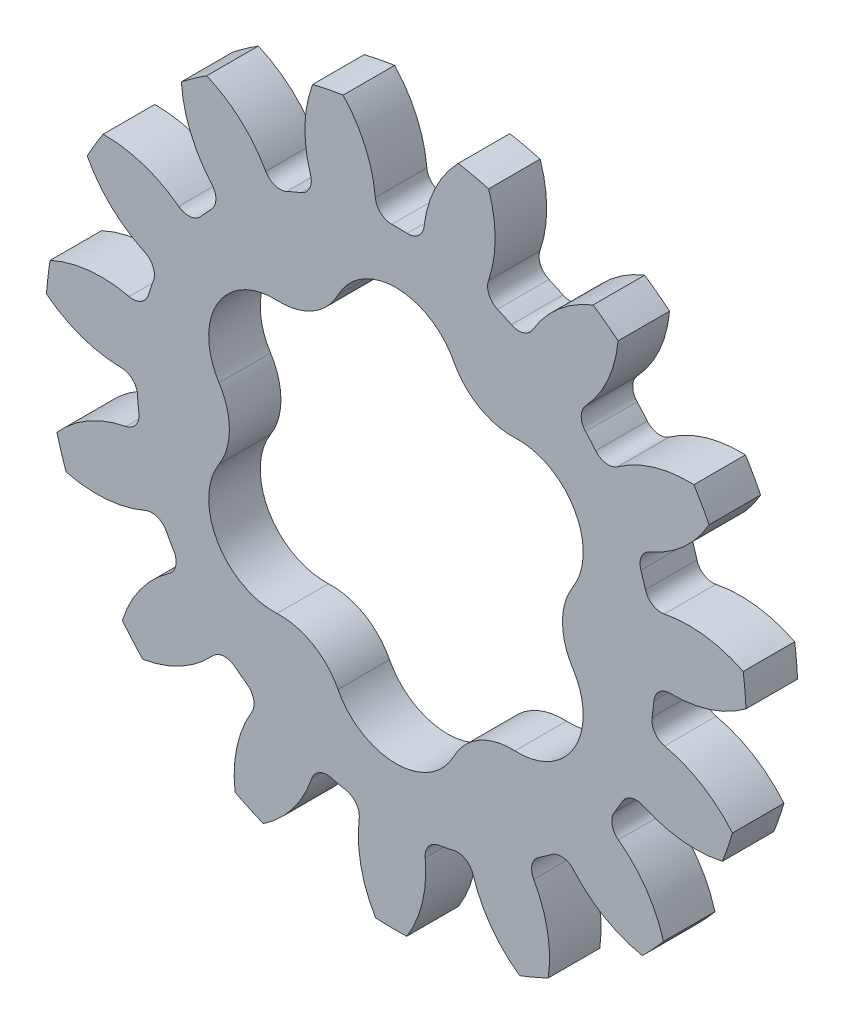
SolidWorks part; units mm, degrees
material "6061-T6 (SS)"
ref_plane "Front" through (0, 0, 0) normal (0, 0, 1) x (1, 0, 0)
ref_plane "Top" through (0, 0, 0) normal (0, 1, 0) x (1, 0, 0)
ref_plane "Right" through (0, 0, 0) normal (1, 0, 0) x (0, 0, -1)
sketch "Sketch3" plane through (0, 0, 0) normal (0, 0, 1) x (1, 0, 0)
  circle A0 centre (0, 0) radius 21.59
  dimension "od" = 43.18
extrude "gearBody" add sketch "Sketch3" along normal blind 3.175
sketch "Sketch2" plane through (0, 0, 0) normal (0, 0, 1) x (1, 0, 0)
  line L0 (0, 0) -> (17.0393, 7.0579) construction
  line L1 (21.9771, -8.1843) -> (0, 0) construction
  line L2 (0, 0) -> (36.3143, 0) construction
  line L3 (19.0486, -0.229) -> (18.5705, -4.2473) construction
  line L5 (18.8096, -2.2381) -> (0, 0) construction
  line L7 (0, 0) -> (18.4432, 0) construction
  arc A0 (18.4395, -0.3701) -> (18.0115, -3.9672) centre (0, 0) ccw construction
  arc A1 (21.5666, 1.0048) -> (20.7286, -6.0375) centre (0, 0) ccw construction
  arc A2 (19.0486, -0.229) -> (18.5705, -4.2473) centre (0, 0) ccw construction
  arc A3 (15.7767, -2.3527) -> (15.8883, -1.4151) centre (0, 0) ccw
  arc A4 (21.9771, -8.1843) -> (16.5518, -3.4814) centre (14.9073, -10.8592) ccw
  arc A5 (21.9771, -8.1843) -> (23.2839, 2.7987) centre (0, 0) ccw
  arc A6 (23.2839, 2.7987) -> (16.9066, -0.4998) centre (17.0393, 7.0579) cw
  arc A7 (15.8883, -1.4151) -> (16.9066, -0.4998) centre (16.8889, -1.5042) cw
  arc A8 (16.5518, -3.4814) -> (15.7767, -2.3527) centre (16.7703, -2.5009) cw
  point P6 (23.2839, 2.7987)
  point P22 (21.9771, -8.1843)
  dimension "baseDia" = 36.8864
  dimension "od" = 43.18
  dimension "pd" = 38.1
  dimension "rd" = 31.9024
  dimension "rFillet" = 1.0046
  dimension "pointX" = 23.2839
  dimension "pointY" = 2.7987
  dimension "CTT" = 4.0183
  dimension "flankCenterAngle" = 22.5
extrude "toothCut" cut sketch "Sketch2" along normal through all
pattern_circular "CirPattern1" count 15 over 360 about axis through (0, 0, 3.175) along (0, 0, -1) of "toothCut"
ref_axis "toothSpace" through (0, 0, 0) along (0.993, -0.1182, 0)
ref_axis "Axis2" through (20.4399, -6.9526, 0) along (-0.9467, 0.322, 0)
sketch "hub1Dia" plane through (0, 0, 0) normal (0, 0, -1) x (-1, 0, 0)
  circle A0 centre (0, 0) radius 12.7
  dimension "hub1Dia" = 25.4
sketch "hub2Dia" plane through (0, 0, 3.175) normal (0, 0, 1) x (1, 0, 0)
  circle A0 centre (0, 0) radius 12.7
  dimension "hub2dia" = 25.4
sketch "boreDia" plane through (0, 0, 0) normal (0, 0, 1) x (1, 0, 0)
  circle A0 centre (0, 0) radius 1.5
  dimension "boreDia" = 3
extrude "bore" cut sketch "boreDia" against normal mid plane 25400
sketch "kwy1sketch" plane through (0, 0, 0) normal (0, 0, 1) x (1, 0, 0)
  line L0 (-5.199, 1.3723) -> (0, 0) construction
  line L1 (29.2504, 5.4145) -> (22.7682, -19.1445)
  line L2 (22.7682, -19.1445) -> (-7.9305, -11.0417)
  line L3 (29.2504, 5.4145) -> (-1.4483, 13.5172)
  line L4 (-7.9305, -11.0417) -> (0, 0)
  line L5 (0, 0) -> (-1.4483, 13.5172)
  line L6 (0, 0) -> (15.8395, -1.8847) construction
  line L7 (26.0093, -6.865) -> (0, 0) construction
  arc A7 (15.7767, -2.3527) -> (15.8883, -1.4151) centre (0, 0) ccw construction
  point P9 (26.0093, -6.865)
  point P13 (-0.8672, 0.2289)
  dimension "kwy1width" = 25.4
  dimension "kwy1depth" = 26.9
  dimension "kwy1angle" = 8
  dimension "kwy1Depth2" = 31.75
sketch "kwy2sketch" plane through (0, 0, 0) normal (0, 0, 1) x (1, 0, 0)
  line L0 (15.8395, -1.8847) -> (0, 0) construction
  line L1 (0, 0) -> (-3.211, -1.8699) construction
  line L2 (16.8545, 24.5117) -> (29.6367, 2.5623)
  line L3 (29.6367, 2.5623) -> (2.2, -13.4154)
  line L4 (16.8545, 24.5117) -> (-10.5822, 8.534)
  line L5 (2.2, -13.4154) -> (0, 0)
  line L6 (0, 0) -> (-10.5822, 8.534)
  arc A2 (15.7767, -2.3527) -> (15.8883, -1.4151) centre (0, 0) ccw construction
  point P10 (23.2456, 13.537)
  dimension "kwy2angle" = 37
  dimension "kwy2Width" = 25.4
  dimension "kwy2depth" = 26.9
  dimension "kwy2Depth2" = 31.75
sketch "kwy3sketch" plane through (0, 0, 0) normal (0, 0, 1) x (1, 0, 0)
  line L0 (15.8395, -1.8847) -> (0, 0) construction
  line L1 (0, 0) -> (-0.686, -2.5992) construction
  line L2 (-5.4145, 29.2504) -> (19.1445, 22.7682)
  line L3 (19.1445, 22.7682) -> (11.0417, -7.9305)
  line L4 (-5.4145, 29.2504) -> (-13.5172, -1.4483)
  line L5 (11.0417, -7.9305) -> (0, 0)
  line L6 (-13.5172, -1.4483) -> (0, 0)
  point P10 (6.865, 26.0093)
  dimension "kwy3angle" = 82
  dimension "kwy3depth" = 26.9
  dimension "kwy3width" = 25.4
  dimension "kwy3Depth2" = 31.75
sketch "kwy4sketch" plane through (0, 0, 0) normal (0, 0, 1) x (1, 0, 0)
  line L0 (15.8395, -1.8847) -> (0, 0) construction
  line L1 (0, 0) -> (1.0577, -1.8163) construction
  line L2 (-2.5623, 29.6367) -> (-24.5117, 16.8545)
  line L3 (-24.5117, 16.8545) -> (-8.534, -10.5822)
  line L4 (-8.534, -10.5822) -> (0, 0)
  line L5 (13.4154, 2.2) -> (0, 0)
  line L6 (-2.5623, 29.6367) -> (13.4154, 2.2)
  point P15 (-13.537, 23.2456)
  dimension "kwy4angle" = 127
  dimension "kwy4depth" = 26.9
  dimension "kwy4width" = 25.4
  dimension "kwy4Depth2" = 31.75
sketch "kwy5sketch" plane through (0, 0, 0) normal (0, 0, 1) x (1, 0, 0)
  line L0 (15.8395, -1.8847) -> (0, 0) construction
  line L1 (0, 0) -> (1.7454, -0.4607) construction
  line L2 (-22.7682, 19.1445) -> (-29.2504, -5.4145)
  line L3 (-29.2504, -5.4145) -> (1.4483, -13.5172)
  line L4 (-22.7682, 19.1445) -> (7.9305, 11.0417)
  line L5 (1.4483, -13.5172) -> (0, 0)
  line L6 (7.9305, 11.0417) -> (0, 0)
  point P10 (-26.0093, 6.865)
  dimension "kwy5width" = 25.4
  dimension "kwy5depth" = 26.9
  dimension "kwy5angle" = 172
  dimension "kwy5Depth2" = 31.75
sketch "kwy6sketch" plane through (0, 0, 0) normal (0, 0, 1) x (1, 0, 0)
  line L0 (15.8395, -1.8847) -> (0, 0) construction
  line L1 (0, 0) -> (1.5587, 0.9077) construction
  line L2 (-29.6367, -2.5623) -> (-16.8545, -24.5117)
  line L3 (-16.8545, -24.5117) -> (10.5822, -8.534)
  line L4 (-29.6367, -2.5623) -> (-2.2, 13.4154)
  line L5 (10.5822, -8.534) -> (0, 0)
  line L6 (-2.2, 13.4154) -> (0, 0)
  point P10 (-23.2456, -13.537)
  dimension "kwy6angle" = 217
  dimension "kwy6width" = 25.4
  dimension "kwy6depth" = 26.9
  dimension "kwy6Depth2" = 31.75
sketch "kwy7sketch" plane through (0, 0, 0) normal (0, 0, 1) x (1, 0, 0)
  line L0 (15.8395, -1.8847) -> (0, 0) construction
  line L1 (0, 0) -> (0.5157, 1.9539) construction
  line L2 (-19.1445, -22.7682) -> (5.4145, -29.2504)
  line L3 (-19.1445, -22.7682) -> (-11.0417, 7.9305)
  line L4 (5.4145, -29.2504) -> (13.5172, 1.4483)
  line L5 (-11.0417, 7.9305) -> (0, 0)
  line L6 (13.5172, 1.4483) -> (0, 0)
  point P10 (-6.865, -26.0093)
  dimension "kwy7angle" = 82
  dimension "kwy7width" = 25.4
  dimension "kwy7depth" = 26.9
  dimension "kwy7angle1" = 262
  dimension "kwy7Depth2" = 31.75
sketch "kwy8sketch" plane through (0, 0, 0) normal (0, 0, 1) x (1, 0, 0)
  line L0 (15.8395, -1.8847) -> (0, 0) construction
  line L1 (0, 0) -> (-0.9035, 1.5514) construction
  line L2 (2.5623, -29.6367) -> (24.5117, -16.8545)
  line L3 (24.5117, -16.8545) -> (8.534, 10.5822)
  line L4 (2.5623, -29.6367) -> (-13.4154, -2.2)
  line L5 (8.534, 10.5822) -> (0, 0)
  line L6 (-13.4154, -2.2) -> (0, 0)
  point P10 (13.537, -23.2456)
  dimension "kwy8angle" = 307
  dimension "kwy8width" = 25.4
  dimension "kwy8depth" = 26.9
  dimension "kwy8Depth2" = 31.75
sketch "centerLine" plane through (0, 0, 0) normal (0, 1, 0) x (1, 0, 0)
  line L0 (0, 36.4807) -> (0, -59.6309) construction
ref_plane "CB1plane" through (0, 0, 0) normal (0, 0, -1) x (-1, 0, 0)
sketch "CB1diameter" plane through (0, 0, 0) normal (0, 0, -1) x (-1, 0, 0)
  circle A0 centre (0, 0) radius 12.7
  dimension "CB1diameter" = 25.4
ref_plane "CB2plane" through (0, 0, 3.175) normal (0, 0, 1) x (1, 0, 0)
sketch "CB2diameter" plane through (0, 0, 3.175) normal (0, 0, 1) x (1, 0, 0)
  circle A0 centre (0, 0) radius 12.7
  dimension "CB2diameter" = 25.4
ref_axis "Axis1" through (0, 0, 50) along (0, 0, -1)
sketch3d "3DSketch1" plane through (0, 0, 0) normal (0, 0, 1) x (1, 0, 0)
sketch "Sketch4" plane through (0, 0, 0) normal (0, 0, -1) x (-1, 0, 0)
  arc A12 (-7.3297, 8.3524) -> (-3.5686, 10.5239) centre (-7.1372, 12.362) ccw
  arc A13 (-7.3297, 8.3524) -> (-10.8983, 2.1715) centre (-7.5222, 4.3429) ccw
  arc A14 (-10.8983, -2.1715) -> (-10.8983, 2.1715) centre (-14.2744, 0) ccw
  arc A15 (-10.8983, -2.1715) -> (-7.3297, -8.3524) centre (-7.5222, -4.3429) ccw
  arc A16 (-3.5686, -10.5239) -> (-7.3297, -8.3524) centre (-7.1372, -12.362) ccw
  arc A17 (-3.5686, -10.5239) -> (3.5686, -10.5239) centre (0, -8.6859) ccw
  arc A18 (7.3297, -8.3524) -> (3.5686, -10.5239) centre (7.1372, -12.362) ccw
  arc A19 (7.3297, -8.3524) -> (10.8983, -2.1715) centre (7.5222, -4.3429) ccw
  arc A20 (10.8983, 2.1715) -> (10.8983, -2.1715) centre (14.2744, 0) ccw
  arc A21 (10.8983, 2.1715) -> (7.3297, 8.3524) centre (7.5222, 4.3429) ccw
  arc A22 (3.5686, 10.5239) -> (7.3297, 8.3524) centre (7.1372, 12.362) ccw
  arc A23 (3.5686, 10.5239) -> (-3.5686, 10.5239) centre (0, 8.6859) ccw
  arc A24 (-7.3297, 8.3524) -> (-3.5686, 10.5239) centre (-7.1372, 12.362) ccw
  arc A25 (-7.3297, 8.3524) -> (-10.8983, 2.1715) centre (-7.5222, 4.3429) ccw
  arc A26 (-10.8983, -2.1715) -> (-10.8983, 2.1715) centre (-14.2744, 0) ccw
  arc A27 (-10.8983, -2.1715) -> (-7.3297, -8.3524) centre (-7.5222, -4.3429) ccw
  arc A28 (-3.5686, -10.5239) -> (-7.3297, -8.3524) centre (-7.1372, -12.362) ccw
  arc A29 (-3.5686, -10.5239) -> (3.5686, -10.5239) centre (0, -8.6859) ccw
  arc A30 (7.3297, -8.3524) -> (3.5686, -10.5239) centre (7.1372, -12.362) ccw
  arc A31 (7.3297, -8.3524) -> (10.8983, -2.1715) centre (7.5222, -4.3429) ccw
  arc A32 (10.8983, 2.1715) -> (10.8983, -2.1715) centre (14.2744, 0) ccw
  arc A33 (10.8983, 2.1715) -> (7.3297, 8.3524) centre (7.5222, 4.3429) ccw
  arc A34 (3.5686, 10.5239) -> (7.3297, 8.3524) centre (7.1372, 12.362) ccw
  arc A35 (3.5686, 10.5239) -> (-3.5686, 10.5239) centre (0, 8.6859) ccw
  dimension "D1" = 0
extrude "Cut-Extrude1" cut sketch "Sketch4" against normal through all
